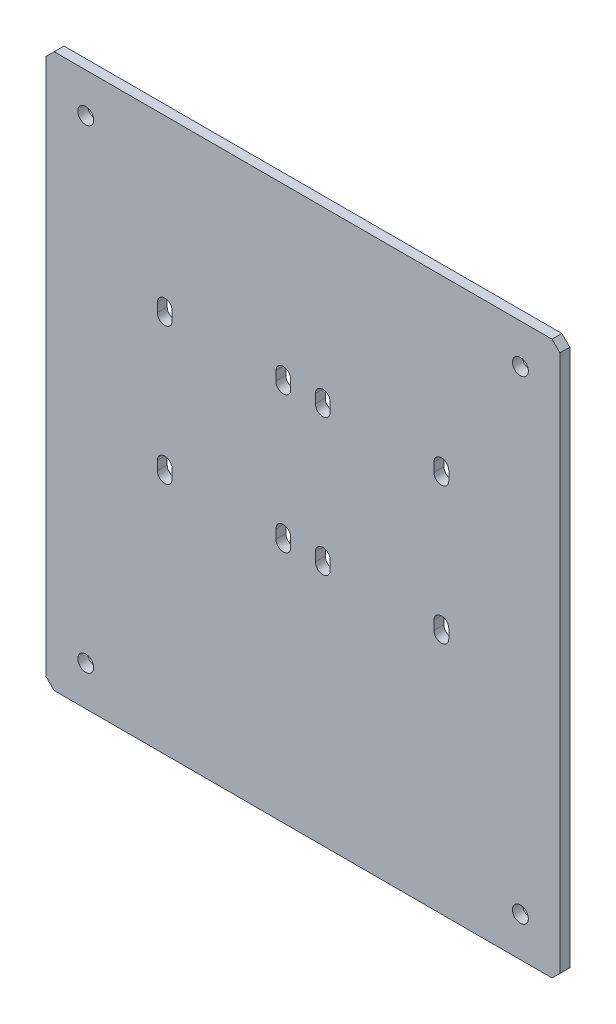
SolidWorks part; units mm, degrees
material "Acrylic (Medium-high impact)"
ref_plane "Front" through (0, 0, 0) normal (0, 0, 1) x (1, 0, 0)
ref_plane "Top" through (0, 0, 0) normal (0, 1, 0) x (1, 0, 0)
ref_plane "Right" through (0, 0, 0) normal (1, 0, 0) x (0, 0, -1)
sketch "Sketch1" plane through (0, 0, 0) normal (0, 0, 1) x (1, 0, 0)
  line L1 (0, 0) -> (165.1, 0)
  line L2 (0, 0) -> (0, 177.8)
  line L3 (0, 177.8) -> (165.1, 177.8)
  line L4 (165.1, 0) -> (165.1, 177.8)
extrude "Boss-Extrude1" add sketch "Sketch1" against normal blind 3.175
sketch "Sketch2" plane through (0, 0, 0) normal (0, 0, 1) x (1, 0, 0)
  line L0 (38.1, 121.7875) -> (38.1, 124.645) construction
  line L1 (35.7187, 121.7875) -> (35.7187, 124.645)
  line L2 (40.4812, 121.7875) -> (40.4812, 124.645)
  line L3 (38.1, 77.7875) -> (38.1, 80.645) construction
  line L4 (35.7187, 77.7875) -> (35.7187, 80.645)
  line L5 (40.4812, 77.7875) -> (40.4812, 80.645)
  line L6 (76.2, 124.645) -> (76.2, 121.7875) construction
  line L7 (78.5812, 124.645) -> (78.5812, 121.7875)
  line L8 (73.8187, 124.645) -> (73.8187, 121.7875)
  line L9 (76.2, 80.645) -> (76.2, 77.7875) construction
  line L10 (78.5812, 80.645) -> (78.5813, 77.7875)
  line L11 (73.8187, 80.645) -> (73.8187, 77.7875)
  line L12 (82.55, 0) -> (82.55, 21.0033) construction
  line L13 (0, 0) -> (165.1, 0) construction
  line L14 (127, 121.7875) -> (127, 124.645) construction
  line L15 (129.3812, 121.7875) -> (129.3812, 124.645)
  line L16 (124.6187, 121.7875) -> (124.6187, 124.645)
  line L17 (127, 77.7875) -> (127, 80.645) construction
  line L18 (129.3812, 77.7875) -> (129.3812, 80.645)
  line L19 (124.6187, 77.7875) -> (124.6187, 80.645)
  line L20 (88.9, 124.645) -> (88.9, 121.7875) construction
  line L21 (86.5187, 124.645) -> (86.5187, 121.7875)
  line L22 (91.2812, 124.645) -> (91.2812, 121.7875)
  line L23 (88.9, 80.645) -> (88.9, 77.7875) construction
  line L24 (86.5187, 80.645) -> (86.5187, 77.7875)
  line L25 (91.2812, 80.645) -> (91.2812, 77.7875)
  arc A0 (35.7187, 121.7875) -> (40.4812, 121.7875) centre (38.1, 121.7875) ccw
  arc A1 (40.4812, 124.645) -> (35.7187, 124.645) centre (38.1, 124.645) ccw
  arc A2 (35.7187, 77.7875) -> (40.4812, 77.7875) centre (38.1, 77.7875) ccw
  arc A3 (40.4812, 80.645) -> (35.7187, 80.645) centre (38.1, 80.645) ccw
  arc A4 (78.5812, 124.645) -> (73.8187, 124.645) centre (76.2, 124.645) ccw
  arc A5 (73.8187, 121.7875) -> (78.5812, 121.7875) centre (76.2, 121.7875) ccw
  arc A6 (78.5812, 80.645) -> (73.8187, 80.645) centre (76.2, 80.645) ccw
  arc A7 (73.8187, 77.7875) -> (78.5813, 77.7875) centre (76.2, 77.7875) ccw
  arc A8 (129.3812, 121.7875) -> (124.6187, 121.7875) centre (127, 121.7875) cw
  arc A9 (124.6187, 124.645) -> (129.3812, 124.645) centre (127, 124.645) cw
  arc A10 (129.3812, 77.7875) -> (124.6187, 77.7875) centre (127, 77.7875) cw
  arc A11 (124.6187, 80.645) -> (129.3812, 80.645) centre (127, 80.645) cw
  arc A12 (86.5187, 124.645) -> (91.2812, 124.645) centre (88.9, 124.645) cw
  arc A13 (91.2812, 121.7875) -> (86.5187, 121.7875) centre (88.9, 121.7875) cw
  arc A14 (86.5187, 80.645) -> (91.2812, 80.645) centre (88.9, 80.645) cw
  arc A15 (91.2812, 77.7875) -> (86.5187, 77.7875) centre (88.9, 77.7875) cw
  point P2 (38.1, 123.2162)
  point P9 (38.1, 79.2162)
  point P16 (76.2, 123.2162)
  point P21 (76.2, 79.2163)
  point P34 (127, 123.2162)
  point P41 (127, 79.2162)
  point P48 (88.9, 123.2162)
  point P55 (88.9, 79.2163)
  point P60 (38.1, 122.7798)
  point P61 (38.1, 123.9364)
  point P62 (38.1, 123.612)
  dimension "D2" = 7.62
  dimension "D4" = 12.7
  dimension "D5" = 44
  dimension "D6" = 77.7875
  dimension "D1" = 4.7625
  dimension "D3" = 38.1
extrude "Cut-Extrude1" cut sketch "Sketch2" against normal through all
sketch "Sketch5" plane through (0, 0, 0) normal (0, 0, 1) x (1, 0, 0)
  line L0 (0, 0) -> (165.1, 0) construction
  line L1 (0, 177.8) -> (0, 0) construction
  line L2 (165.1, 177.8) -> (0, 177.8) construction
  line L3 (165.1, 0) -> (165.1, 177.8) construction
  point P0 (12.7, 12.7)
  point P2 (12.7, 165.1)
  point P4 (152.4, 165.1)
  point P6 (152.4, 12.7)
  dimension "D1" = 12.7
  dimension "D2" = 12.7
  dimension "D3" = 12.7
  dimension "D4" = 12.7
hole_wizard "#10 Clearance Hole1" positions "Sketch5" profile "Sketch4" hole size "#10" standard "ANSI Inch" end condition through all
sketch "Sketch4" plane through (12.7, 12.7, 0) normal (1, 0, 0) x (0, -1, 0)
  line L0 (0, 0) -> (0, 3.175)
  line L1 (0, 3.175) -> (2.5527, 3.175)
  line L2 (2.5527, 3.175) -> (2.5527, 0)
  line L5 (2.5527, 0) -> (0, 0)
  line L11 (0, -6.35) -> (0, 107.95) construction
  dimension "Thru Hole Dia." = 5.1054
  dimension "Thru Hole Depth" = 3.175
chamfer "Chamfer1" distance 2.54 angle 45 4 edges at (0, 0, -1.5875) (165.1, 0, -1.5875) (165.1, 177.8, -1.5875) (0, 177.8, -1.5875)
